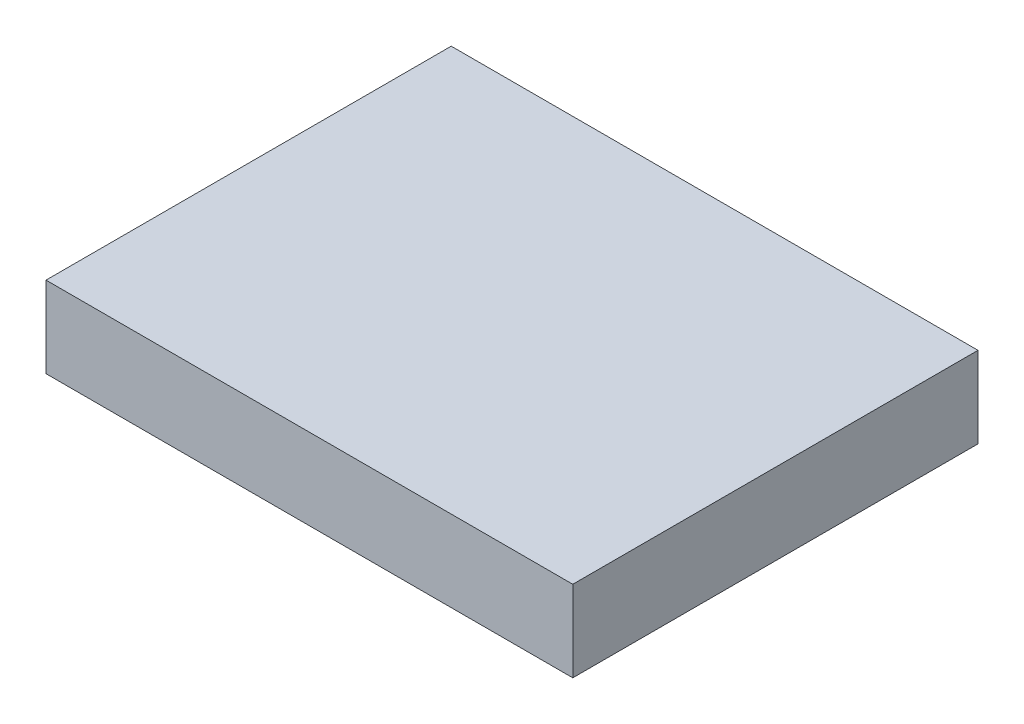
SolidWorks part; units mm, degrees
ref_plane "Front Plane" through (0, 0, 0) normal (0, 0, 1) x (1, 0, 0)
ref_plane "Top Plane" through (0, 0, 0) normal (0, 1, 0) x (1, 0, 0)
ref_plane "Right Plane" through (0, 0, 0) normal (1, 0, 0) x (0, 0, -1)
sketch "Sketch1" plane through (0, 0, 0) normal (0, 1, 0) x (1, 0, 0)
  line L0 (0, 0) -> (330.2, 0)
  line L1 (330.2, 0) -> (330.2, 203.2)
  line L2 (0, 0) -> (0, 203.2)
  line L3 (165.1, 0) -> (165.1, 254)
  line L4 (0, 203.2) -> (0, 254)
  line L5 (0, 254) -> (330.2, 254)
  line L6 (330.2, 254) -> (330.2, 203.2)
  arc A0 (0, 203.2) -> (165.1, 254) centre (158.3572, -17.7734) cw construction
  arc A1 (330.2, 203.2) -> (165.1, 254) centre (169.8499, -24.2503) ccw construction
  point P8 (165.1, 0)
  dimension "D1" = 330.2
  dimension "D2" = 203.2
  dimension "D3" = 254
extrude "Boss-Extrude1" add sketch "Sketch1" along normal blind 50.8 contours L5 L4 L2 L0 L3 | L6 L5 L3 L0 L1 region at (82.55, 0, -127) region at (247.65, 0, -127)
